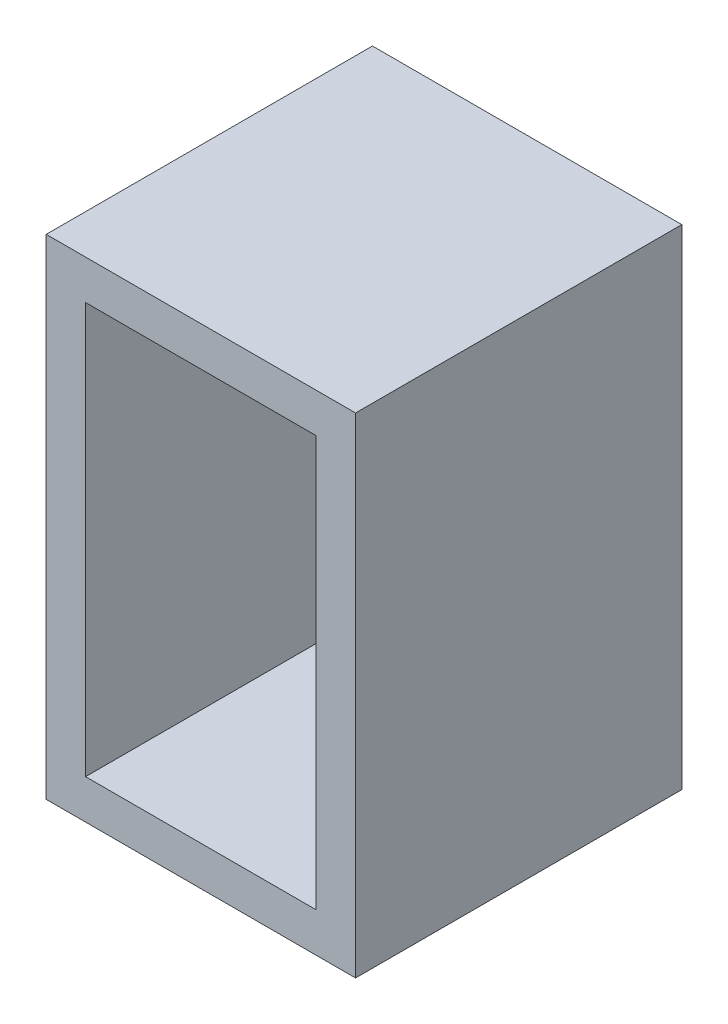
SolidWorks part; units mm, degrees
ref_plane "Front Plane" through (0, 0, 0) normal (0, 0, 1) x (1, 0, 0)
ref_plane "Top Plane" through (0, 0, 0) normal (0, 1, 0) x (1, 0, 0)
ref_plane "Right Plane" through (0, 0, 0) normal (1, 0, 0) x (0, 0, -1)
sketch "Sketch1" plane through (0, 0, 0) normal (0, 0, 1) x (1, 0, 0)
  line L1 (10.25, 18.25) -> (-10.25, 18.25)
  line L2 (10.25, 18.25) -> (10.25, -18.25)
  line L3 (10.25, -18.25) -> (-10.25, -18.25)
  line L4 (-10.25, 18.25) -> (-10.25, -18.25)
  line L5 (10.25, 18.25) -> (-10.25, -18.25) construction
  line L6 (10.25, -18.25) -> (-10.25, 18.25) construction
  line L7 (12.25, 20.25) -> (-12.25, 20.25)
  line L8 (12.25, 20.25) -> (12.25, -20.25)
  line L9 (12.25, -20.25) -> (-12.25, -20.25)
  line L10 (-12.25, 20.25) -> (-12.25, -20.25)
  line L11 (12.25, 20.25) -> (-12.25, -20.25) construction
  line L12 (12.25, -20.25) -> (-12.25, 20.25) construction
  point P0 (0, 0)
  point P6 (0, 0)
  dimension "D1" = 20.5
  dimension "D2" = 36.5
  dimension "D3" = 2
  dimension "D4" = 2
extrude "Boss-Extrude1" add sketch "Sketch1" along normal blind 27
extrude "Boss-Extrude2" add sketch "Sketch1<2>" against normal blind 2 contours L1 L4 L3 L2 | L7 L10 L9 L8 L4 L1 L2 L3 region at (0, 0, 0) region at (11.7767, 0, 0)
sketch "Sketch1<2>" plane through (0, 0, 0) normal (0, 0, 1) x (1, 0, 0) same geometry as "Sketch1"
sketch "Sketch2" plane through (0, 0, -2) normal (0, 0, -1) x (-1, 0, 0)
  line L0 (-10.25, 6.75) -> (-1.25, 6.75)
  line L1 (10.25, 18.25) -> (-10.25, 18.25)
  line L2 (10.25, 18.25) -> (10.25, -18.25)
  line L3 (10.25, -18.25) -> (-10.25, -18.25)
  line L4 (-10.25, 18.25) -> (-10.25, -18.25)
  line L5 (10.25, 18.25) -> (-10.25, -18.25) construction
  line L6 (10.25, -18.25) -> (-10.25, 18.25) construction
  line L7 (-1.25, 6.75) -> (-1.25, -15.25)
  line L8 (-1.25, -15.25) -> (-10.25, -15.25)
  point P0 (0, 0)
  dimension "D1" = 20.5
  dimension "D2" = 36.5
  dimension "D3" = 3
  dimension "D4" = 9
  dimension "D5" = 22
extrude "Cut-Extrude1" cut sketch "Sketch2" against normal up to surface (2 mm away) contours L8 L7 L0 L4 region at (5.75, -4.25, -2) up to face at (0, 0, 0)
sketch "Sketch3" plane through (0, 0, -2) normal (0, 0, -1) x (-1, 0, 0)
  line L0 (-1.25, 6.75) -> (-1.25, -15.25) construction
  line L1 (-1.25, -4.25) -> (-10.25, -4.25) construction
  line L2 (-10.25, 6.75) -> (-10.25, -15.25) construction
  line L3 (-11.75, 8.25) -> (-11.75, 9.45)
  line L4 (-10.25, 6.75) -> (-1.25, 6.75) construction
  line L5 (-5.75, 6.75) -> (-5.75, -15.25) construction
  line L6 (-1.25, -15.25) -> (-10.25, -15.25) construction
  line L7 (0.25, 8.25) -> (-11.75, 8.25)
  line L8 (0.25, 8.25) -> (0.25, -16.75)
  line L9 (0.25, -16.75) -> (-11.75, -16.75)
  line L10 (-11.75, 8.25) -> (-11.75, -16.75)
  line L11 (0.25, 8.25) -> (-11.75, -16.75) construction
  line L12 (0.25, -16.75) -> (-11.75, 8.25) construction
  line L13 (1.45, 9.45) -> (-12.95, 9.45)
  line L14 (1.45, 9.45) -> (1.45, -17.95)
  line L15 (1.45, -17.95) -> (-12.95, -17.95)
  line L16 (-12.95, 9.45) -> (-12.95, -17.95)
  line L17 (1.45, 9.45) -> (-12.95, -17.95) construction
  line L18 (1.45, -17.95) -> (-12.95, 9.45) construction
  line L19 (-11.75, -16.75) -> (-11.75, -17.95)
  line L20 (0.25, 8.25) -> (1.45, 8.25)
  line L21 (0.25, -16.75) -> (1.45, -16.75)
  point P12 (-5.75, -4.25)
  point P17 (-5.75, -4.25)
  dimension "D1" = 1.5
  dimension "D2" = 1.5
  dimension "D3" = 1.2
  dimension "D4" = 1.2
extrude "Cut-Extrude2" cut sketch "Sketch3" against normal up to surface (2 mm away) contours L7 L20 L14 L13 L3 region at (5.15, 8.85, -2) up to face at (2.875, -2.125, 0)
sketch "Sketch4" plane through (0, 0, -2) normal (0, 0, -1) x (-1, 0, 0)
  line L0 (12.25, 20.25) -> (12.25, -20.25) construction
  line L1 (13.75, 21.75) -> (-13.75, 21.75)
  line L2 (13.75, 21.75) -> (13.75, -21.75)
  line L3 (13.75, -21.75) -> (-13.75, -21.75)
  line L4 (-13.75, 21.75) -> (-13.75, -21.75)
  line L5 (13.75, 21.75) -> (-13.75, -21.75) construction
  line L6 (13.75, -21.75) -> (-13.75, 21.75) construction
  line L7 (-12.25, 20.25) -> (12.25, 20.25) construction
  line L9 (12.25, 20.25) -> (-12.25, 20.25)
  line L10 (12.25, 20.25) -> (12.25, -20.25)
  line L11 (12.25, -20.25) -> (-12.25, -20.25)
  line L12 (-12.25, 20.25) -> (-12.25, -20.25)
  line L13 (12.25, 20.25) -> (-12.25, -20.25) construction
  line L14 (12.25, -20.25) -> (-12.25, 20.25) construction
  point P0 (0, 0)
  point P10 (0, 0)
  dimension "D1" = 1.5
  dimension "D2" = 1.5
extrude "Boss-Extrude3" add sketch "Sketch4" against normal up to surface (29 mm away) up to face at (0, 0, 27)
sketch "Sketch5" plane through (0, 0, 0) normal (0, 0, 1) x (1, 0, 0)
  line L0 (1.25, 6.75) -> (1.25, 8.25)
  line L1 (-1.45, 8.25) -> (10.25, 8.25) construction
  line L2 (1.25, 8.25) -> (10.25, 8.25)
  line L3 (10.25, 8.25) -> (10.25, 6.75)
  line L4 (10.25, 6.75) -> (1.25, 6.75)
extrude "Cut-Extrude3" cut sketch "Sketch5" against normal up to surface (2 mm away) up to face at (5.75, -4.25, -2)
